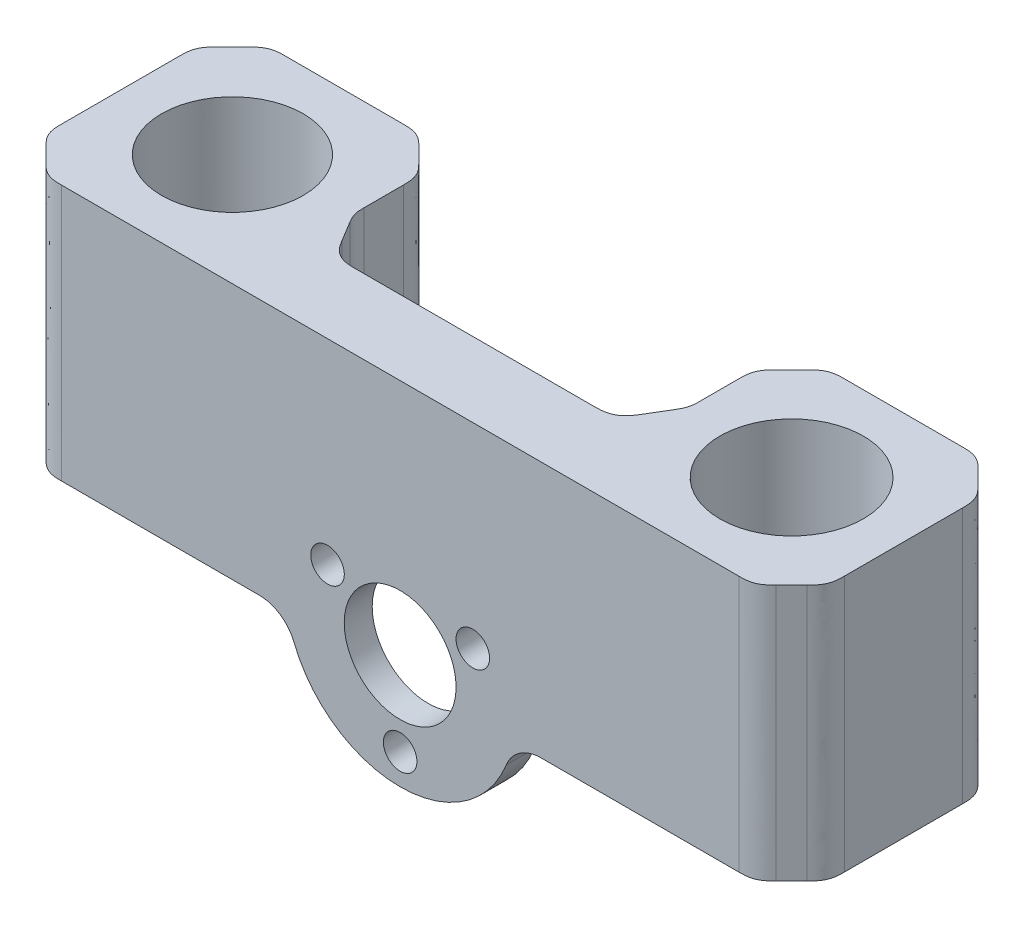
SolidWorks part; units mm, degrees
ref_plane "Plan de face" through (0, 0, 0) normal (0, 0, 1) x (1, 0, 0)
ref_plane "Plan de dessus" through (0, 0, 0) normal (0, 1, 0) x (1, 0, 0)
ref_plane "Plan de droite" through (0, 0, 0) normal (1, 0, 0) x (0, 0, -1)
sketch "Esquisse1" plane through (0, 0, 0) normal (0, 1, 0) x (1, 0, 0)
  line L1 (-26, -12) -> (26, -12)
  line L2 (0, 0) -> (0, -4) construction
  line L3 (15, -4) -> (-15, -4)
  line L4 (-18, 8) -> (-18, 12) construction
  line L5 (-18, 12) -> (-22, 12) construction
  line L6 (-22, 12) -> (-18, 8)
  line L7 (-22, 12) -> (-38, 12)
  line L8 (-38, 8) -> (-38, 12) construction
  line L9 (-38, 8) -> (-42, 8) construction
  line L10 (-42, 8) -> (-38, 12)
  line L11 (-42, 8) -> (-42, 0)
  line L12 (-18, 1) -> (-18, -4) construction
  line L13 (-18, 1) -> (-15, -4)
  line L17 (-42, 0) -> (-30, 0) construction
  line L18 (-42, 0) -> (-42, -8)
  line L19 (-42, -8) -> (-38, -8) construction
  line L20 (-38, -8) -> (-38, -12) construction
  line L21 (-42, -8) -> (-38, -12)
  line L22 (-38, -12) -> (-26, -12)
  line L24 (0, -12) -> (0, -4) construction
  line L25 (-30, 0) -> (0, 0) construction
  line L26 (0, -55) -> (0, 55) construction
  line L27 (38, -8) -> (38, -12) construction
  line L28 (42, -8) -> (38, -8) construction
  line L29 (42, 0) -> (30, 0) construction
  line L30 (18, -4) -> (15, -4) construction
  line L31 (18, -4) -> (18, 1) construction
  line L32 (38, 8) -> (42, 8) construction
  line L33 (38, 8) -> (38, 12) construction
  line L34 (18, 12) -> (22, 12) construction
  line L35 (18, 8) -> (18, 12) construction
  line L45 (-18, 1) -> (-18, 8)
  line L46 (18, 1) -> (18, 8)
  line L47 (38, -12) -> (26, -12)
  line L48 (42, -8) -> (38, -12)
  line L49 (42, 0) -> (42, -8)
  line L50 (18, 1) -> (15, -4)
  line L51 (42, 8) -> (42, 0)
  line L52 (42, 8) -> (38, 12)
  line L53 (22, 12) -> (38, 12)
  line L54 (22, 12) -> (18, 8)
  line L56 (-18, -4) -> (-15, -4) construction
  circle A0 centre (-30, 0) radius 7.6
  circle A2 centre (30, 0) radius 7.6
  dimension "D3" = 15.2
  dimension "D4" = 4
  dimension "D15" = 30
  dimension "D2" = 4
  dimension "D5" = 4
  dimension "D6" = 4
  dimension "D7" = 15
  dimension "D8" = 3
  dimension "D9" = 8
  dimension "D10" = 8
  dimension "D11" = 4
  dimension "D12" = 4
  dimension "D13" = 12
  dimension "D14" = 5
extrude "Boss.-Extru.1" add sketch "Esquisse1" along normal blind 25
sketch "Esquisse3" plane through (0, 0, 0) normal (0, -1, 0) x (1, 0, 0)
  line L0 (30, 0) -> (-30, 0) construction
  line L1 (0, -55) -> (0, 55) construction
  circle A0 centre (-30, 0) radius 7.6
  circle A1 centre (-30, 0) radius 4.4
  circle A2 centre (30, 0) radius 4.4
  circle A3 centre (30, 0) radius 7.6
  point P8 (0, 0)
  dimension "D2" = 15.2
  dimension "D3" = 8.8
  dimension "D1" = 30
extrude "Boss.-Extru.3" add sketch "Esquisse3" along normal blind 2.5 separate body
extrude "Boss.-Extru.5" add sketch "Esquisse1<4>" against normal blind 2.5
sketch "Esquisse1<4>" plane through (0, 0, 0) normal (0, 1, 0) x (1, 0, 0) same geometry as "Esquisse1"
fillet "Congé1" radius 4 16 edges at (-42, 11.25, 8) (-42, 11.25, -8) (-38, 11.25, -12) (-22, 11.25, -12) (-38, 11.25, 12) (-18, 11.25, -8) (38, 11.25, 12) (42, 11.25, 8) (42, 11.25, -8) (38, 11.25, -12) (22, 11.25, -12) (18, 11.25, -8) (18, 11.25, -1) (15, 11.25, 4) (-15, 11.25, 4) (-18, 11.25, -1) curvature continuous yes
sketch "Esquisse7" plane through (0, 0, 4) normal (0, 0, -1) x (-1, 0, 0)
  line L0 (0, 9.5) -> (0, -0.5) construction
  line L1 (-12.7352, 25) -> (12.7352, 25) construction
  line L3 (0, 9.5) -> (0, 25) construction
  line L4 (0, -0.5) -> (0, -9.5) construction
  line L5 (0, -0.5) -> (-7.7942, 4) construction
  line L6 (0, -0.5) -> (7.7942, 4) construction
  circle A0 centre (0, -0.5) radius 12.25
  circle A1 centre (0, -0.5) radius 9 construction
  circle A2 centre (-7.7942, 4) radius 1.8
  circle A3 centre (7.7942, 4) radius 1.8
  circle A4 centre (0, -9.5) radius 1.8
  circle A5 centre (0, -0.5) radius 6
  line M4 (-12.7352, -2.5) -> (12.7352, -2.5)
  dimension "D2" = 24.5
  dimension "D3" = 18
  dimension "D6" = 10
  dimension "D1" = 15.5
  dimension "D4" = 120
  dimension "D5" = 120
extrude "Enlèv. mat.-Extru.1" cut sketch "Esquisse7" against normal blind 5 contours A0 A3 A2 M4 region at (-11.9264, -1.4802, 4)
sketch "Esquisse10" plane through (0, 0, 12) normal (0, 0, 1) x (1, 0, 0)
  line L0 (-36.3431, -2.5) -> (36.3431, -2.5) construction
  line L1 (12.0856, -2.5) -> (-12.0856, -2.5)
  arc A0 (-12.0856, -2.5) -> (12.0856, -2.5) centre (0, -0.5) ccw
extrude "Boss.-Extru.9" add sketch "Esquisse10" against normal blind 3
extrude "Enlèv. mat.-Extru.2" cut sketch "Esquisse7<4>" against normal through all contours A4 | A2 | A3 | A5 M4 | A5 M4 region at (0, -4.1569, 4) region at (0, 1.0067, 4) region at (7.7942, 4, 4) region at (-7.7942, 4, 4) region at (0, -9.5, 4)
sketch "Esquisse7<4>" plane through (0, 0, 4) normal (0, 0, -1) x (-1, 0, 0) same geometry as "Esquisse7"
sketch "Esquisse11" plane through (0, 25, 0) normal (0, 1, 0) x (1, 0, 0)
  circle A0 centre (-30, 0) radius 7.6
  circle A1 centre (30, 0) radius 7.7
  dimension "D1" = 15.2
extrude "Enlèv. mat.-Extru.3" cut sketch "Esquisse11" against normal blind 24
fillet "Congé5" radius 4 2 edges at (-12.0856, -2.5, 10.5) (12.0856, -2.5, 10.5)
fillet "Congé9" radius 4 1 edges at (-12.0856, -2.5, 6.5) type face fillet first side face at (-30, -2.5, -4.4) second side face at (0, 4.625, 6.5)
